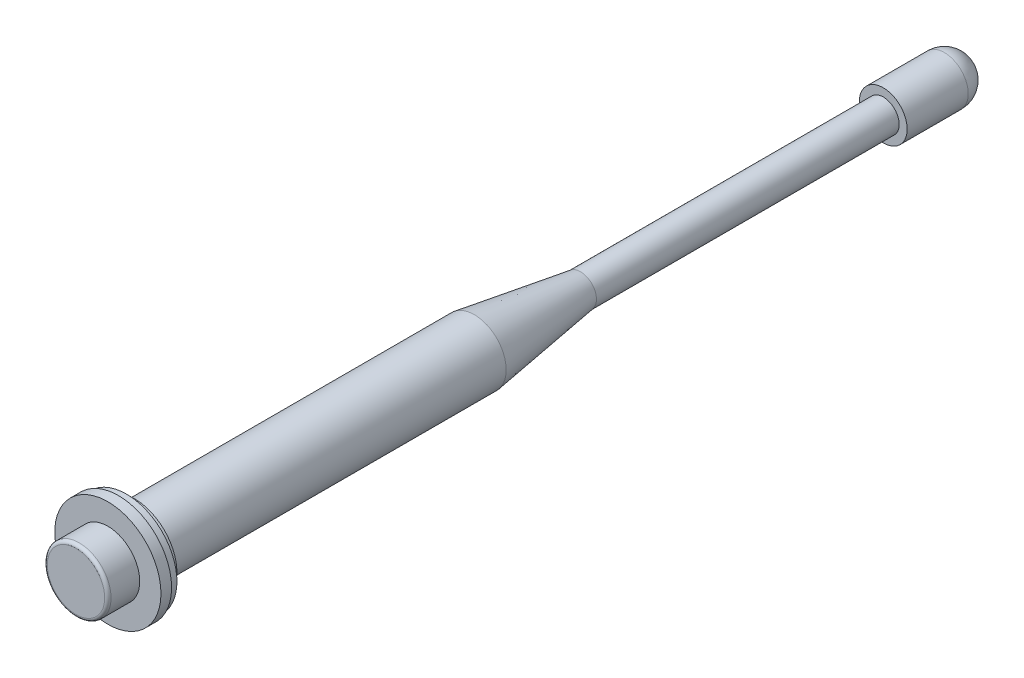
SolidWorks part; units mm, degrees
material "AISI 304"
ref_plane "Front Plane" through (0, 0, 0) normal (0, 0, 1) x (1, 0, 0)
ref_plane "Top Plane" through (0, 0, 0) normal (0, 1, 0) x (1, 0, 0)
ref_plane "Right Plane" through (0, 0, 0) normal (1, 0, 0) x (0, 0, -1)
other "Configuration Table"
sketch "Sketch1" plane through (0, 0, 0) normal (1, 0, 0) x (0, 0, -1)
  line L0 (0, 1.5) -> (-10, 3)
  line L1 (28.5, 0) -> (0, 0)
  line L2 (28.5, 0) -> (28.5, 1.5)
  line L3 (28.5, 1.5) -> (0, 1.5)
  line L4 (0, 0) -> (0, 1.5)
  line L5 (-10, 3) -> (-47.5, 3)
  line L6 (-47.5, 3) -> (-47.5, 0)
  line L7 (-47.5, 0) -> (0, 0)
  line L8 (28.5, 1.5) -> (28.5, 2.25)
  line L9 (28.5, 2.25) -> (34.25, 2.25)
  line L10 (36.5, 0) -> (32.5, 0)
  line L11 (28.5, 0) -> (32.5, 0)
  line L12 (28.5, 0) -> (28.5, 1.25)
  line L13 (28.5, 1.25) -> (32.5, 1.25)
  line L14 (32.5, 0) -> (32.5, 1.25)
  arc A0 (34.25, 2.25) -> (36.5, 0) centre (34.25, 0) cw
  dimension "D5" = 1.25
  dimension "D1" = 84
  dimension "D2" = 8
  dimension "D3" = 4
  dimension "D4" = 2.25
  dimension "D6" = 28.5
  dimension "D7" = 3
  dimension "D8" = 10
  dimension "D9" = 1.5
revolve "Revolve1" add sketch "Sketch1" angle 360 about L1 region at (0, 1.4444, 24.8843) region at (0, 0.75, -14.25) region at (0, 0.625, -30.5)
fillet "Fillet1" radius 0.3 1 edges at (-3, 0, 47.5)
thread "Thread1" pitch 0.45 method extrude profile "Thread Profile1" start angle 0, offset 0, length 3, pitch 0.45, diameter 2.5
ref_plane "Plane1" through (1.25, 0, -32.5) normal (0, -1, 0) x (1, 0, 0)
sketch "Thread Profile1" plane through (1.25, 0, -32.5) normal (0, -1, 0) x (1, 0, 0)
  line L0 (0, 0) -> (0, 0.45) construction
  line L1 (0, 0) -> (0.2436, 0.1406)
  line L2 (0.2436, 0.1406) -> (0.2436, 0.1969)
  line L3 (0.2436, 0.1969) -> (0, 0.3375)
  line L4 (0.2436, 0.1687) -> (0, 0.1687) construction
  line L11 (0, 0) -> (0, 0.3375)
  point P2 (0, 0)
  dimension "Pitch" = 0.45
  dimension "Profile_Angle" = 60
  dimension "Profile_Land" = 0.0562
  dimension "Profile_Height" = 0.2436
ref_plane "Plane2" through (0, 0, 44.5) normal (0, 0, 1) x (1, 0, 0)
sketch "Sketch4" plane through (0, 0, 44.5) normal (0, 0, 1) x (1, 0, 0)
  circle A0 centre (0, 0) radius 5
  dimension "D1" = 10
extrude "Boss-Extrude1" add sketch "Sketch4" against normal blind 1 separate body
sketch "Sketch5" plane through (0, 0, 44.5) normal (0, 0, 1) x (1, 0, 0)
  circle A0 centre (0, 0) radius 4
  dimension "D1" = 8
sketch "Sketch6" plane through (0, 0, 43.5) normal (0, 0, -1) x (-1, 0, 0)
  circle A0 centre (0, 0) radius 4.75
  dimension "D1" = 9.5
extrude "Boss-Extrude3" add sketch "Sketch6" along normal blind 0.75 separate body
sketch "Sketch7" plane through (0, 0, 42.75) normal (0, 0, -1) x (-1, 0, 0)
  circle A0 centre (0, 0) radius 4
  dimension "D1" = 8
extrude "Boss-Extrude4" add sketch "Sketch7" along normal blind 0.75
sketch "Sketch8" plane through (0, 0, 42) normal (0, 0, -1) x (-1, 0, 0)
  circle A0 centre (0, 0) radius 3 construction
  circle A1 centre (0, 0) radius 3
extrude "Cut-Extrude2" cut sketch "Sketch8" against normal blind 6.75
revolve "Revolve2" add sketch "Sketch1<3>" angle 360 about L1 region at (0, 1.2781, -33.0204) other way angle 360
sketch "Sketch1<3>" plane through (0, 0, 0) normal (1, 0, 0) x (0, 0, -1) same geometry as "Sketch1"
